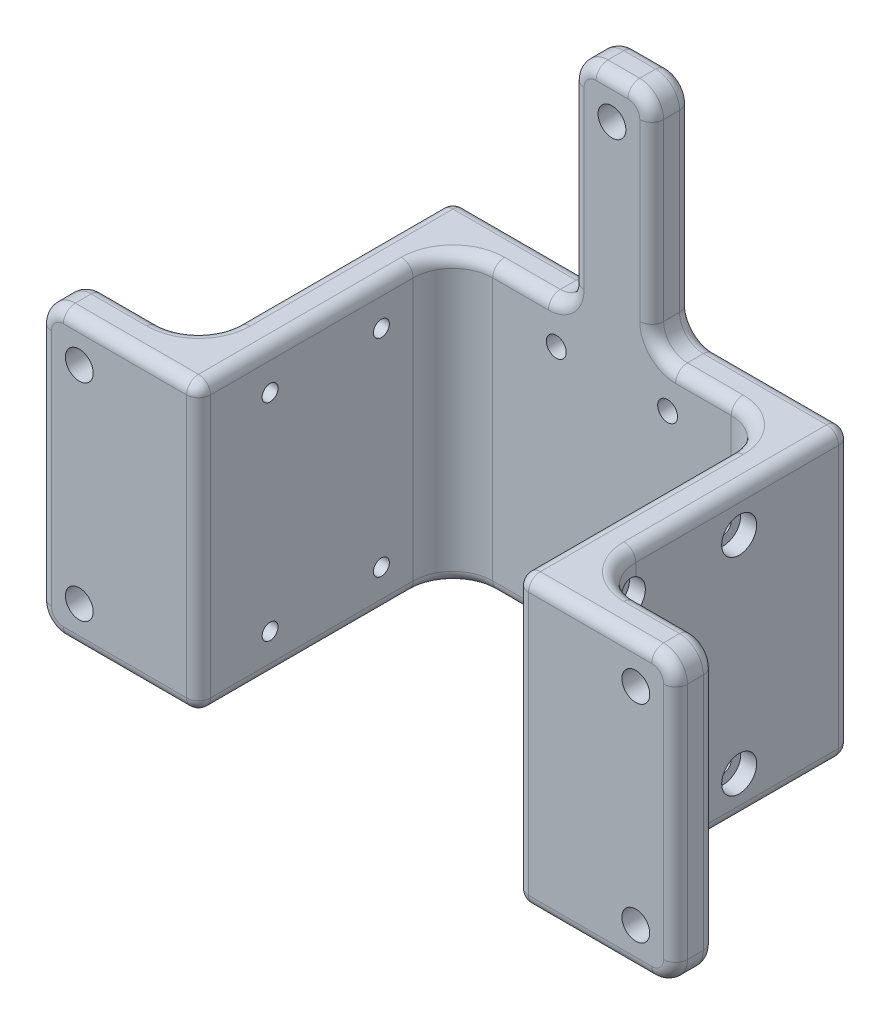
SolidWorks part; units mm, degrees
ref_plane "正面" through (0, 0, 0) normal (0, 0, 1) x (1, 0, 0)
ref_plane "平面" through (0, 0, 0) normal (0, 1, 0) x (1, 0, 0)
ref_plane "右側面" through (0, 0, 0) normal (1, 0, 0) x (0, 0, -1)
sketch "ｽｹｯﾁ1" plane through (0, 0, 0) normal (0, 0, 1) x (1, 0, 0)
  line L0 (0, -18) -> (0, 29) construction
  line L1 (25, 18) -> (-25, 18)
  line L2 (25, 18) -> (25, -18)
  line L3 (25, -18) -> (-25, -18)
  line L4 (-25, 18) -> (-25, -18)
  line L5 (25, 18) -> (-25, -18) construction
  line L6 (25, -18) -> (-25, 18) construction
  point P0 (0, 0)
  dimension "D1" = 50
  dimension "D2" = 36
  dimension "D3" = 11
extrude "ﾎﾞｽ - 押し出し1" add sketch "ｽｹｯﾁ1" along normal blind 5
sketch "ｽｹｯﾁ2" plane through (0, 0, 0) normal (0, 0, -1) x (-1, 0, 0)
  line L0 (0, 18) -> (0, -18) construction
  line L3 (-25, 18) -> (25, 18) construction
  line L4 (25, -18) -> (-25, -18) construction
  line L5 (-25, 0) -> (25, 0) construction
  line L6 (-25, -18) -> (-25, 18) construction
  line L7 (25, 18) -> (25, -18) construction
  circle A0 centre (-7, 13) radius 1.25
  circle A1 centre (7, 13) radius 1.25
  circle A2 centre (7, -13) radius 1.25
  circle A3 centre (-7, -13) radius 1.25
  dimension "D1" = 2.5
  dimension "D3" = 13
  dimension "D2" = 7
extrude "ｶｯﾄ - 押し出し1" cut sketch "ｽｹｯﾁ2" against normal blind 5
sketch "ｽｹｯﾁ3" plane through (0, 0, 0) normal (0, 0, -1) x (-1, 0, 0)
  line L0 (0, 18) -> (0, -18) construction
  line L1 (-25, 18) -> (25, 18) construction
  line L2 (25, -18) -> (-25, -18) construction
  line L3 (-25, 0) -> (25, 0) construction
  line L4 (-25, -18) -> (-25, 18) construction
  line L5 (25, 18) -> (25, -18) construction
  circle A0 centre (-7, 13) radius 2.2
  circle A1 centre (7, 13) radius 2.2
  circle A2 centre (7, -13) radius 2.2
  circle A3 centre (-7, -13) radius 2.2
  dimension "D1" = 4.4
extrude "ｶｯﾄ - 押し出し2" cut sketch "ｽｹｯﾁ3" against normal blind 2
sketch "ｽｹｯﾁ8" plane through (25, 0, 0) normal (1, 0, 0) x (0, 0, -1)
  line L0 (-21, 18) -> (-21, -18) construction
  line L1 (-5, 18) -> (-37, 18)
  line L2 (-5, 18) -> (-5, -18)
  line L3 (-5, -18) -> (-37, -18)
  line L4 (-37, 18) -> (-37, -18)
  line L5 (-37, 0) -> (-5, 0) construction
  circle A0 centre (-28, 13) radius 1
  circle A1 centre (-14, 13) radius 1
  circle A2 centre (-14, -13) radius 1
  circle A3 centre (-28, -13) radius 1
  dimension "D2" = 2
  dimension "D3" = 7
  dimension "D4" = 13
  dimension "D1" = 32
extrude "ﾎﾞｽ - 押し出し3" add sketch "ｽｹｯﾁ8" against normal blind 5
sketch "ｽｹｯﾁ9" plane through (25, 0, 0) normal (1, 0, 0) x (0, 0, -1)
  line L0 (-21, 18) -> (-21, -18) construction
  line L1 (-46, 0) -> (4, 0) construction
  circle A0 centre (-28, 13) radius 2.2
  circle A1 centre (-14, 13) radius 2.2
  circle A2 centre (-14, -13) radius 2.2
  circle A3 centre (-28, -13) radius 2.2
extrude "ｶｯﾄ - 押し出し4" cut sketch "ｽｹｯﾁ9" against normal blind 2
sketch "ｽｹｯﾁ10" plane through (0, 0, 37) normal (0, 0, 1) x (1, 0, 0)
  line L0 (25, 18) -> (25, -18) construction
  line L1 (25, 18) -> (40, 18)
  line L3 (25, -18) -> (40, -18)
  line L4 (40, 18) -> (40, -18)
  line L5 (20, 0) -> (40, 0) construction
  line L6 (25, 18) -> (25, -18)
  circle A0 centre (35, 13) radius 1.75
  circle A1 centre (35, -13) radius 1.75
  dimension "D3" = 3.5
  dimension "D4" = 13
  dimension "D5" = 10
  dimension "D1" = 36
  dimension "D2" = 15
extrude "ﾎﾞｽ - 押し出し4" add sketch "ｽｹｯﾁ10" against normal blind 5
sketch "ｽｹｯﾁ11" plane through (-25, 0, 0) normal (-1, 0, 0) x (0, 0, 1)
  line L0 (21, 18) -> (21, -18) construction
  line L1 (37, 18) -> (5, 18)
  line L2 (37, 18) -> (37, -18)
  line L3 (37, -18) -> (5, -18)
  line L4 (5, 18) -> (5, -18)
  line L5 (5, 0) -> (37, 0) construction
  circle A0 centre (14, 13) radius 1
  circle A1 centre (28, 13) radius 1
  circle A2 centre (28, -13) radius 1
  circle A3 centre (14, -13) radius 1
extrude "ﾎﾞｽ - 押し出し5" add sketch "ｽｹｯﾁ11" against normal blind 5
sketch "ｽｹｯﾁ12" plane through (-25, 0, 0) normal (-1, 0, 0) x (0, 0, 1)
  line L0 (21, 18) -> (21, -18) construction
  line L1 (-4, 0) -> (46, 0) construction
  circle A0 centre (14, 13) radius 2.2
  circle A1 centre (28, 13) radius 2.2
  circle A2 centre (28, -13) radius 2.2
  circle A3 centre (14, -13) radius 2.2
extrude "ｶｯﾄ - 押し出し5" cut sketch "ｽｹｯﾁ12" against normal blind 2
sketch "ｽｹｯﾁ18" plane through (0, 0, 37) normal (0, 0, 1) x (1, 0, 0)
  line L0 (-25, -18) -> (-25, 18) construction
  line L1 (-40, 18) -> (-25, 18)
  line L2 (-40, 18) -> (-40, -18)
  line L3 (-40, -18) -> (-25, -18)
  line L4 (-25, 18) -> (-25, -18)
  line L5 (-40, 0) -> (-25, 0) construction
  circle A0 centre (-35, 13) radius 1.75
  circle A1 centre (-35, -13) radius 1.75
  dimension "D3" = 10
  dimension "D1" = 15
  dimension "D2" = 0
extrude "ﾎﾞｽ - 押し出し6" add sketch "ｽｹｯﾁ18" against normal blind 5
sketch "ｽｹｯﾁ20" plane through (0, 0, 32) normal (0, 0, -1) x (-1, 0, 0)
  circle A0 centre (-35, 13) radius 3.2
  circle A1 centre (-35, -13) radius 3.2
  dimension "D1" = 6.4
  dimension "D2" = 6.4
extrude "ｶｯﾄ - 押し出し8" cut sketch "ｽｹｯﾁ20" against normal blind 2.5
sketch "ｽｹｯﾁ21" plane through (0, 0, 32) normal (0, 0, -1) x (-1, 0, 0)
  circle A0 centre (35, 13) radius 3.2
  circle A1 centre (35, -13) radius 3.2
  dimension "D1" = 6.4
  dimension "D2" = 6.4
extrude "ｶｯﾄ - 押し出し9" cut sketch "ｽｹｯﾁ21" against normal blind 2.5
fillet "ﾌｨﾚｯﾄ2" radius 5 4 edges at (-20, 0, 5)
sketch "ｽｹｯﾁ22" plane through (0, 0, 0) normal (0, 0, -1) x (-1, 0, 0)
  line L0 (0, -18) -> (0, 32)
  line L1 (5, 46) -> (-5, 46)
  line L2 (5, 46) -> (5, 18)
  line L3 (-5, 46) -> (-5, 18)
  line L4 (5, 46) -> (-5, 18) construction
  line L5 (5, 18) -> (-5, 46) construction
  circle A0 centre (0, 41) radius 1.75
extrude "ﾎﾞｽ - 押し出し7" add sketch "ｽｹｯﾁ22" against normal blind 5
fillet "ﾌｨﾚｯﾄ3" radius 3 4 edges
sketch "ｽｹｯﾁ23" plane through (0, 0, 0) normal (0, 0, -1) x (-1, 0, 0)
  circle A0 centre (0, 41) radius 3.2
  dimension "D1" = 6.4
extrude "ｶｯﾄ - 押し出し10" cut sketch "ｽｹｯﾁ23" against normal blind 2.5
fillet "ﾌｨﾚｯﾄ6" radius 3 4 edges at (-40, 18, 34.5) (-40, -18, 34.5) (40, -18, 34.5) (40, 18, 34.5)
fillet "ﾌｨﾚｯﾄ7" radius 3 2 edges at (5, 46, 2.5) (-5, 46, 2.5)
fillet "ﾌｨﾚｯﾄ8" radius 1.5 60 edges at (-20, 0, 37) (-28.5, 18, 37) (-28.5, -18, 37) (-20, 18, 23.5) (-20, -18, 23.5) (18.5355, 18, 6.4645) (18.5355, -18, 6.4645) (-18.5355, -18, 6.4645) (-18.5355, 18, 6.4645) (26.4645, -18, 30.5355) (26.4645, 18, 30.5355) (-26.4645, 18, 30.5355) (-26.4645, -18, 30.5355) (-5.8787, 18.8787, 0) (-5.8787, 18.8787, 5) (5.8787, 18.8787, 0) (5.8787, 18.8787, 5) (-40, 0, 37) (-39.1213, -17.1213, 37) (-39.1213, 17.1213, 37) (-40, 0, 32) (-39.1213, -17.1213, 32) (-39.1213, 17.1213, 32) (40, 0, 37) (39.1213, 17.1213, 37) (39.1213, -17.1213, 37) (40, 0, 32) (39.1213, 17.1213, 32) (39.1213, -17.1213, 32) (0, 46, 0) (0, 46, 5) (-4.1213, 45.1213, 0) (4.1213, 45.1213, 0) (-4.1213, 45.1213, 5) (4.1213, 45.1213, 5) (25, 0, 0) (0, -18, 0) (20, 0, 37) (28.5, -18, 37) (-25, 0, 0) (28.5, 18, 37)
